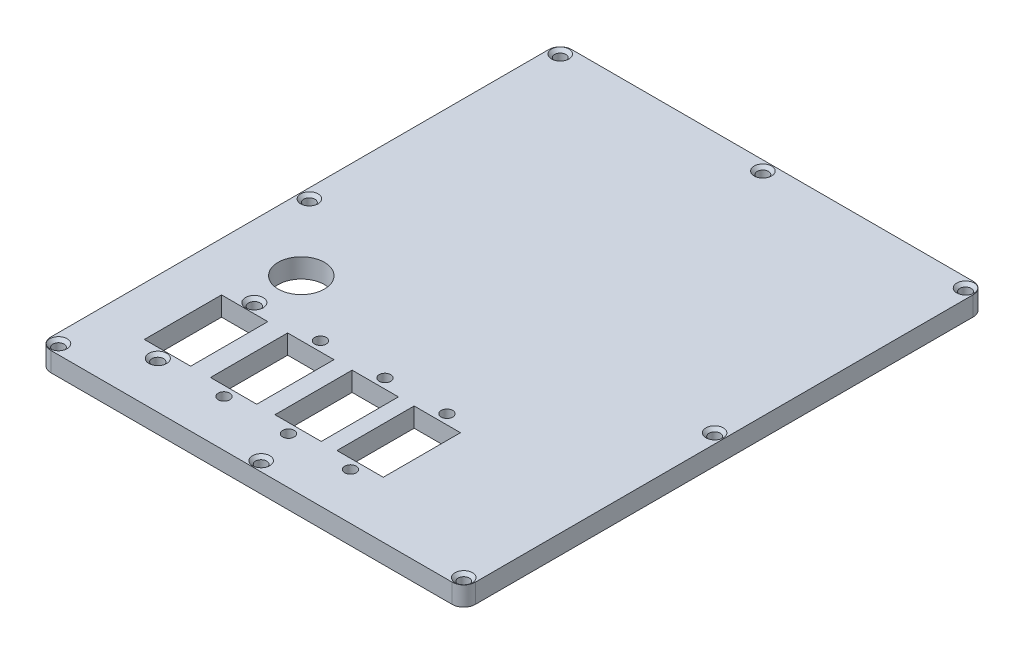
SolidWorks part; units mm, degrees
material "Nylon 6/10"
ref_plane "前视基准面" through (0, 0, 0) normal (0, 0, 1) x (1, 0, 0)
ref_plane "上视基准面" through (0, 0, 0) normal (0, 1, 0) x (1, 0, 0)
ref_plane "右视基准面" through (0, 0, 0) normal (1, 0, 0) x (0, 0, -1)
sketch "Sketch1" plane through (0, 0, 0) normal (0, 1, 0) x (1, 0, 0)
  line L0 (-55, 67.5) -> (55, 67.5)
  line L1 (-50, 62.5) -> (50, 62.5)
  line L2 (-50, 62.5) -> (-50, -62.5)
  line L3 (-50, -62.5) -> (50, -62.5)
  line L4 (50, 62.5) -> (50, -62.5)
  line L5 (-50, 62.5) -> (50, -62.5) construction
  line L6 (-50, -62.5) -> (50, 62.5) construction
  line L7 (55, 67.5) -> (55, -67.5)
  line L8 (-55, -67.5) -> (55, -67.5)
  line L9 (-55, 67.5) -> (-55, -67.5)
  point P0 (0, 0)
  dimension "D1" = 100
  dimension "D2" = 125
  dimension "D3" = 5
extrude "Boss-Extrude1" add sketch "Sketch1" along normal blind 140
sketch "Sketch2" plane through (0, 140, 0) normal (0, 1, 0) x (1, 0, 0)
  line L4 (-55, 67.5) -> (-55, -67.5)
  line L5 (-55, -67.5) -> (55, -67.5)
  line L6 (55, -67.5) -> (55, 67.5)
  line L7 (55, 67.5) -> (-55, 67.5)
  line L8 (-55, 67.5) -> (-55, -67.5)
  line L9 (-55, -67.5) -> (55, -67.5)
  line L10 (55, -67.5) -> (55, 67.5)
  line L11 (55, 67.5) -> (-55, 67.5)
  dimension "D1" = 0
extrude "Boss-Extrude2" add sketch "Sketch2" along normal blind 5
sketch "Sketch3" plane through (0, 0, 0) normal (0, -1, 0) x (1, 0, 0)
  line L0 (50, -62.5) -> (-50, -62.5) construction
  line L1 (50, 62.5) -> (50, -62.5) construction
  line L2 (-50, 62.5) -> (50, 62.5) construction
  line L3 (-50, -62.5) -> (-50, 62.5) construction
  line L4 (-55, 67.5) -> (-55, -67.5)
  line L5 (-55, -67.5) -> (55, -67.5)
  line L6 (55, -67.5) -> (55, 67.5)
  line L7 (55, 67.5) -> (-55, 67.5)
  line L8 (-55, 67.5) -> (-55, -67.5)
  line L9 (-55, -67.5) -> (55, -67.5)
  line L10 (55, -67.5) -> (55, 67.5)
  line L11 (55, 67.5) -> (-55, 67.5)
  line L12 (50, -62.5) -> (-50, -62.5)
  line L13 (50, 62.5) -> (50, -62.5)
  line L14 (-50, 62.5) -> (50, 62.5)
  line L15 (-50, -62.5) -> (-50, 62.5)
  line L16 (-52.5, 65) -> (52.5, 65)
  line L17 (52.5, 65) -> (52.5, -65)
  line L18 (52.5, -65) -> (-52.5, -65)
  line L19 (-52.5, -65) -> (-52.5, 65)
  circle A1 centre (0, 65) radius 1.45
  circle A2 centre (-52.5, 65) radius 1.45
  circle A3 centre (-52.5, -65) radius 1.45
  circle A4 centre (52.5, -65) radius 1.45
  circle A5 centre (52.5, 65) radius 1.45
  circle A6 centre (52.5, 0) radius 1.45
  circle A7 centre (-52.5, 0) radius 1.45
  circle A8 centre (0, -65) radius 1.45
  dimension "D2" = 2.5
  dimension "D1" = 0
extrude "Cut-Extrude1" cut sketch "Sketch3" against normal blind 12 contours L18 A8 | L18 A8 | L18 A4 L17 | L17 A4 L18 | L17 A6 | L17 A6 | L16 A5 L17 | L17 A5 L16 | L16 A1 | L16 A1 | L19 A2 L16 | L16 A2 L19 | L19 A7 | L19 A7 | L19 A3 L18 | L18 A3 L19 region at (-52.7051, 0, 65.2051) region at (-51.8846, 0, 64.3846) region at (0, 0, 65.6154) region at (0, 0, 64.3846) region at (-51.8846, 0, 0) region at (-53.1154, 0, 0) region at (52.7051, 0, 65.2051) region at (51.8846, 0, 64.3846) region at (-51.8846, 0, -64.3846) region at (-52.7051, 0, -65.2051) region at (53.1154, 0, 0) region at (51.8846, 0, 0) region at (0, 0, -64.3846) region at (0, 0, -65.6154) region at (52.7051, 0, -65.2051) region at (51.8846, 0, -64.3846)
sketch "Sketch4" plane through (0, 145, 0) normal (0, 1, 0) x (1, 0, 0)
  line L4 (55, 67.5) -> (-55, 67.5)
  line L5 (-55, 67.5) -> (-55, -67.5)
  line L6 (-55, -67.5) -> (55, -67.5)
  line L7 (55, -67.5) -> (55, 67.5)
  line L8 (55, 67.5) -> (-55, 67.5)
  line L9 (-55, 67.5) -> (-55, -67.5)
  line L10 (-55, -67.5) -> (55, -67.5)
  line L11 (55, -67.5) -> (55, 67.5)
  dimension "D1" = 0
extrude "Cut-Extrude2" cut sketch "Sketch4" against normal blind 140
sketch "Sketch6" plane through (0, 0, 0) normal (0, -1, 0) x (1, 0, 0)
  line L0 (50, -62.5) -> (-50, -62.5) construction
  line L1 (50, 62.5) -> (50, -62.5) construction
  line L2 (-50, 62.5) -> (50, 62.5) construction
  line L3 (-50, -62.5) -> (-50, 62.5) construction
  line L4 (50, -62.5) -> (-50, -62.5)
  line L5 (50, 62.5) -> (50, -62.5)
  line L6 (-50, 62.5) -> (50, 62.5)
  line L7 (-50, -62.5) -> (-50, 62.5)
extrude "Boss-Extrude3" add sketch "Sketch6" against normal blind 5
fillet "Fillet1" radius 3 4 edges at (-55, 2.5, 67.5) (-55, 2.5, -67.5) (55, 2.5, -67.5) (55, 2.5, 67.5)
sketch "Sketch7" plane through (0, 0, 0) normal (0, -1, 0) x (1, 0, 0)
  line L0 (50, 62.5) -> (-50, 62.5)
  line L1 (-50, 62.5) -> (-50, -62.5)
  line L2 (-50, -62.5) -> (50, -62.5)
  line L3 (50, -62.5) -> (50, 62.5)
  line L4 (52, 67.5) -> (-52, 67.5)
  line L5 (-55, 64.5) -> (-55, -64.5)
  line L6 (-52, -67.5) -> (52, -67.5)
  line L7 (55, -64.5) -> (55, 64.5)
  line L8 (52, 67.5) -> (-52, 67.5)
  line L9 (-55, 64.5) -> (-55, -64.5)
  line L10 (-52, -67.5) -> (52, -67.5)
  line L11 (55, -64.5) -> (55, 64.5)
  line L12 (49, 61.5) -> (-49, 61.5)
  line L13 (-49, 61.5) -> (-49, -61.5)
  line L14 (-49, -61.5) -> (49, -61.5)
  line L15 (49, -61.5) -> (49, 61.5)
  arc A0 (-50, 62.5) -> (-50, 62.5) centre (-50, 62.5) ccw
  arc A1 (-50, -62.5) -> (-50, -62.5) centre (-50, -62.5) ccw
  arc A2 (50, -62.5) -> (50, -62.5) centre (50, -62.5) ccw
  arc A3 (50, 62.5) -> (50, 62.5) centre (50, 62.5) ccw
  arc A4 (-52, 67.5) -> (-55, 64.5) centre (-52, 64.5) ccw
  arc A5 (-55, -64.5) -> (-52, -67.5) centre (-52, -64.5) ccw
  arc A6 (52, -67.5) -> (55, -64.5) centre (52, -64.5) ccw
  arc A7 (55, 64.5) -> (52, 67.5) centre (52, 64.5) ccw
  arc A8 (-52, 67.5) -> (-55, 64.5) centre (-52, 64.5) ccw
  arc A9 (-55, -64.5) -> (-52, -67.5) centre (-52, -64.5) ccw
  arc A10 (52, -67.5) -> (55, -64.5) centre (52, -64.5) ccw
  arc A11 (55, 64.5) -> (52, 67.5) centre (52, 64.5) ccw
  arc A12 (-49, 61.5) -> (-49, 61.5) centre (-49, 61.5) ccw
  arc A13 (-49, -61.5) -> (-49, -61.5) centre (-49, -61.5) ccw
  arc A14 (49, -61.5) -> (49, -61.5) centre (49, -61.5) ccw
  arc A15 (49, 61.5) -> (49, 61.5) centre (49, 61.5) ccw
  dimension "D1" = 0
  dimension "D2" = 5
  dimension "D3" = 1
extrude "Cut-Extrude3" cut sketch "Sketch7" against normal blind 1 contours L2 L3 L0 L1 L15 L14 L13 L12 region at (49.8399, 0, 0)
fillet "Fillet2" radius 1 8 edges at (-50, 0.5, 62.5) (-49, 0.5, 61.5) (-49, 0.5, -61.5) (-50, 0.5, -62.5) (50, 0.5, -62.5) (49, 0.5, -61.5) (50, 0.5, 62.5) (49, 0.5, 61.5)
sketch "Sketch8" plane through (0, 0, 0) normal (0, -1, 0) x (1, 0, 0)
  line L0 (-8.5305, 52.8919) -> (3.4695, 52.8919)
  line L5 (-25.2318, 52.8919) -> (-13.2318, 52.8919)
  line L6 (-25.2318, 52.8919) -> (-25.2318, 32.8919)
  line L7 (-42.3374, 52.9235) -> (-30.3374, 52.9235)
  line L8 (-42.3374, 52.9235) -> (-42.3374, 32.9235)
  line L9 (-42.3374, 32.9235) -> (-30.3374, 32.9235)
  line L10 (-30.3374, 52.9235) -> (-30.3374, 32.9235)
  line L11 (-25.2318, 32.8919) -> (-13.2318, 32.8919)
  line L12 (-13.2318, 52.8919) -> (-13.2318, 32.8919)
  line L13 (-8.5305, 52.8919) -> (-8.5305, 32.8919)
  line L14 (-8.5305, 32.8919) -> (3.4695, 32.8919)
  line L15 (3.4695, 52.8919) -> (3.4695, 32.8919)
  line L16 (7.5381, 52.8919) -> (19.5381, 52.8919)
  line L17 (7.5381, 52.8919) -> (7.5381, 32.8919)
  line L18 (7.5381, 32.8919) -> (19.5381, 32.8919)
  line L19 (19.5381, 52.8919) -> (19.5381, 32.8919)
  circle A0 centre (-36.3374, 55.4235) radius 1.5
  circle A1 centre (-36.3374, 30.4235) radius 1.5
  circle A2 centre (-19.2318, 55.3919) radius 1.5
  circle A3 centre (-19.2318, 30.3919) radius 1.5
  circle A4 centre (-2.5305, 55.3919) radius 1.5
  circle A5 centre (-2.5305, 30.3919) radius 1.5
  circle A6 centre (13.5381, 55.3919) radius 1.5
  circle A7 centre (13.5381, 30.3919) radius 1.5
  point P0 (-36.3374, 42.9235)
  point P1 (-19.2318, 42.8919)
  point P4 (-19.2318, 42.8919)
  point P7 (-36.3374, 42.9235)
  point P20 (-2.5305, 42.8919)
  point P23 (-2.5305, 42.8919)
  point P30 (13.5381, 42.8919)
  point P33 (13.5381, 42.8919)
  dimension "D3" = 12
  dimension "D1" = 12
  dimension "D2" = 20
  dimension "D4" = 20
extrude "Cut-Extrude4" cut sketch "Sketch8" against normal blind 12 contours L8 L9 L7 | L9 L7 | L10 L7 L9 | A0 | A0 | A1 | A1 | L5 L12 L11 L6 | A3 | A2 | A4 | L0 L15 L14 L13 | A5 | A6 | L16 L19 L18 L17 | A7 region at (-36.3374, 0, 42.9235) region at (-36.3374, 0, 55.4235) region at (-36.3374, 0, 30.4235)
sketch "Sketch9" plane through (0, 0, 0) normal (0, -1, 0) x (1, 0, 0)
  circle A0 centre (-36.3107, 18.284) radius 6
  point P2 (-36.3107, 18.284)
  point P3 (0, 0)
extrude "Cut-Extrude5" cut sketch "Sketch9" against normal blind 10
chamfer "Chamfer1" distance 0.8 angle 45 10 edges at (-36.3374, 5, 31.9235) (-36.3374, 5, 56.9235) (-52.5, 5, -63.55) (0, 5, -63.55) (52.5, 5, -63.55) (52.5, 5, 1.45) (52.5, 5, 66.45) (0, 5, 66.45) (-52.5, 5, 66.45) (-52.5, 5, 1.45)
